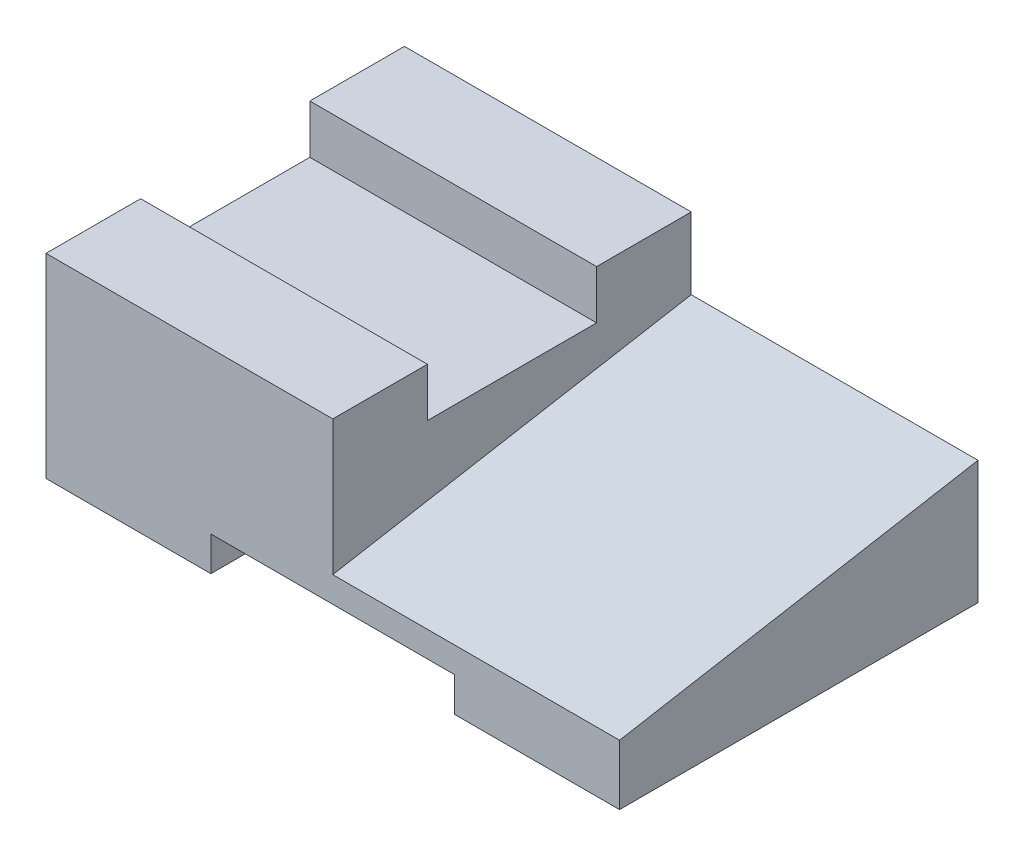
SolidWorks part; units mm, degrees
ref_plane "Front Plane" through (0, 0, 0) normal (0, 0, 1) x (1, 0, 0)
ref_plane "Top Plane" through (0, 0, 0) normal (0, 1, 0) x (1, 0, 0)
ref_plane "Right Plane" through (0, 0, 0) normal (1, 0, 0) x (0, 0, -1)
sketch "Sketch1" plane through (0, 0, 0) normal (0, 0, 1) x (1, 0, 0)
  line L0 (0, 0) -> (0, 37.3267) construction
  line L1 (-100, 0) -> (100, 0)
  line L2 (-100, 0) -> (-100, 68)
  line L3 (-100, 68) -> (100, 68)
  line L4 (100, 0) -> (100, 68)
  line L6 (-42.5, 0) -> (42.5, 0)
  line L7 (-42.5, 0) -> (-42.5, 12)
  line L8 (-42.5, 12) -> (42.5, 12)
  line L9 (42.5, 0) -> (42.5, 12)
  point P4 (0, 0)
  point P12 (0, 12)
  point P13 (0, 0)
  dimension "D1" = 68
  dimension "D2" = 200
  dimension "D3" = 85
  dimension "D4" = 12
extrude "Boss-Extrude1" add sketch "Sketch1" against normal blind 125 contours L9 L1 L4 L3 L2 L7 L8 region at (0, 36.2703, 0)
sketch "Sketch2" plane through (100, 0, 0) normal (1, 0, 0) x (0, 0, -1)
  line L0 (0, 68) -> (33, 68)
  line L1 (125, 68) -> (0, 68) construction
  line L2 (33, 68) -> (33, 51)
  line L3 (33, 51) -> (92, 51)
  line L4 (92, 51) -> (92, 68)
  line L5 (92, 68) -> (125, 68)
  line L6 (125, 68) -> (125, 43)
  line L7 (125, 0) -> (125, 68) construction
  line L8 (125, 43) -> (0, 20.9591)
  line L9 (0, 0) -> (0, 68) construction
  line L10 (0, 20.9591) -> (0, 68)
  line L11 (125, 43) -> (0, 43)
  line M1 (0, 68) -> (0, 0)
  line M3 (125, 0) -> (125, 68)
  line M4 (125, 68) -> (0, 68)
  dimension "D1" = 25
  dimension "D2" = 10
  dimension "D3" = 33
  dimension "D4" = 17
extrude "Cut-Extrude1" cut sketch "Sketch2" against normal blind 100 contours L8 L11 L10 | L3 L4 L2 M4 | L11 L4 L3 L2 M3 M4 M1 region at (100, 66.7252, -16.5) region at (100, 59.5, -62.5) region at (100, 35.653, -41.6667)
extrude "Cut-Extrude2" cut sketch "Sketch2<3>" against normal through all contours L3 L4 L2 M4 region at (100, 59.5, -62.5)
sketch "Sketch2<3>" plane through (100, 0, 0) normal (1, 0, 0) x (0, 0, -1) same geometry as "Sketch2"
